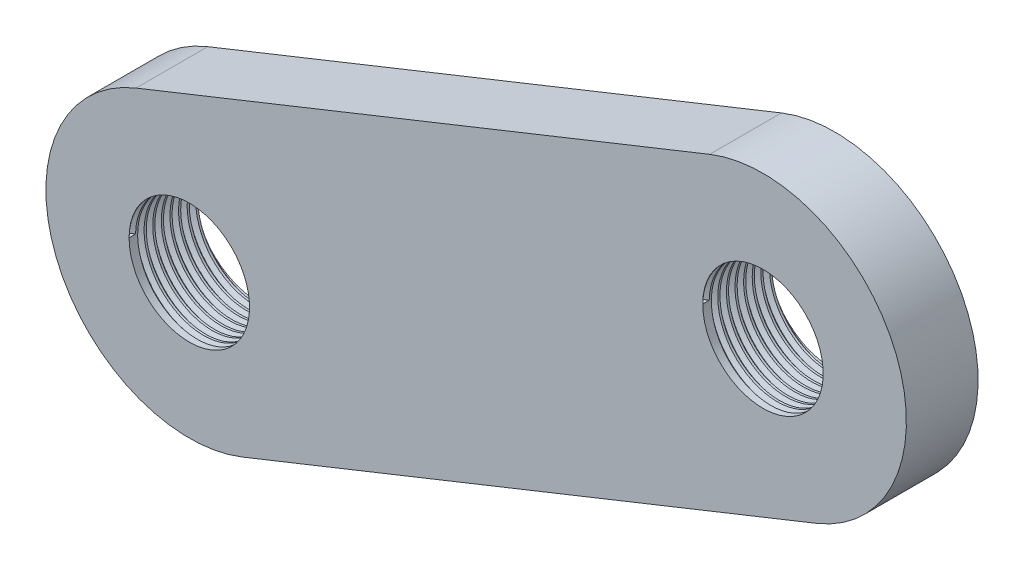
SolidWorks part; units mm, degrees
material "6061-T6 (SS)"
ref_plane "Alzado" through (0, 0, 0) normal (0, 0, 1) x (1, 0, 0)
ref_plane "Planta" through (0, 0, 0) normal (0, 1, 0) x (1, 0, 0)
ref_plane "Vista lateral" through (0, 0, 0) normal (1, 0, 0) x (0, 0, -1)
ref_plane "Plano1" through (0, 0, 51.9) normal (0, 0, 1) x (1, 0, 0)
sketch "Sk_Biela_interior" plane through (0, 0, 51.9) normal (0, 0, 1) x (1, 0, 0)
  line L0 (-42.143, -54.6424) -> (-22.143, -46.6424)
  line L1 (-25.857, -37.3576) -> (-45.857, -45.3576)
  arc A0 (-22.143, -46.6424) -> (-25.857, -37.3576) centre (-24, -42) ccw
  arc A1 (-45.857, -45.3576) -> (-42.143, -54.6424) centre (-44, -50) ccw
  circle A2 centre (-24, -42) radius 2.1
  circle A3 centre (-44, -50) radius 2.1
extrude "Biela_interior" add sketch "Sk_Biela_interior" along normal blind 2.5
thread "Rosca1" pitch 0.3 method cut profile "Perfil de rosca1" start angle 0, offset 0, length 0, pitch 0.3, diameter 4.2
ref_plane "Plano2" through (-26.1, -42, 54.4) normal (0, -1, 0) x (-1, 0, 0)
sketch "Perfil de rosca1" plane through (-26.1, -42, 54.4) normal (0, -1, 0) x (-1, 0, 0)
  line L0 (0, 0) -> (0, 0.3) construction
  line L1 (0, 0) -> (0.1624, 0.0937)
  line L2 (0.1624, 0.0937) -> (0.1624, 0.1312)
  line L3 (0.1624, 0.1312) -> (0, 0.225)
  line L4 (0.1624, 0.1125) -> (0, 0.1125) construction
  line L11 (0, 0) -> (0, 0.225)
  point P2 (0, 0)
  dimension "Pitch" = 0.3
  dimension "Profile_Angle" = 60
  dimension "Profile_Land" = 0.0375
  dimension "Profile_Height" = 0.1624
thread "Rosca2" pitch 0.3 method cut profile "Perfil de rosca2" start angle 0, offset 0, length 0, pitch 0.3, diameter 4.2
ref_plane "Plano3" through (-46.1, -50, 54.4) normal (0, -1, 0) x (-1, 0, 0)
sketch "Perfil de rosca2" plane through (-46.1, -50, 54.4) normal (0, -1, 0) x (-1, 0, 0)
  line L0 (0, 0) -> (0, 0.3) construction
  line L1 (0, 0) -> (0.1624, 0.0937)
  line L2 (0.1624, 0.0937) -> (0.1624, 0.1312)
  line L3 (0.1624, 0.1312) -> (0, 0.225)
  line L4 (0.1624, 0.1125) -> (0, 0.1125) construction
  line L11 (0, 0) -> (0, 0.225)
  point P2 (0, 0)
  dimension "Pitch" = 0.3
  dimension "Profile_Angle" = 60
  dimension "Profile_Land" = 0.0375
  dimension "Profile_Height" = 0.1624
